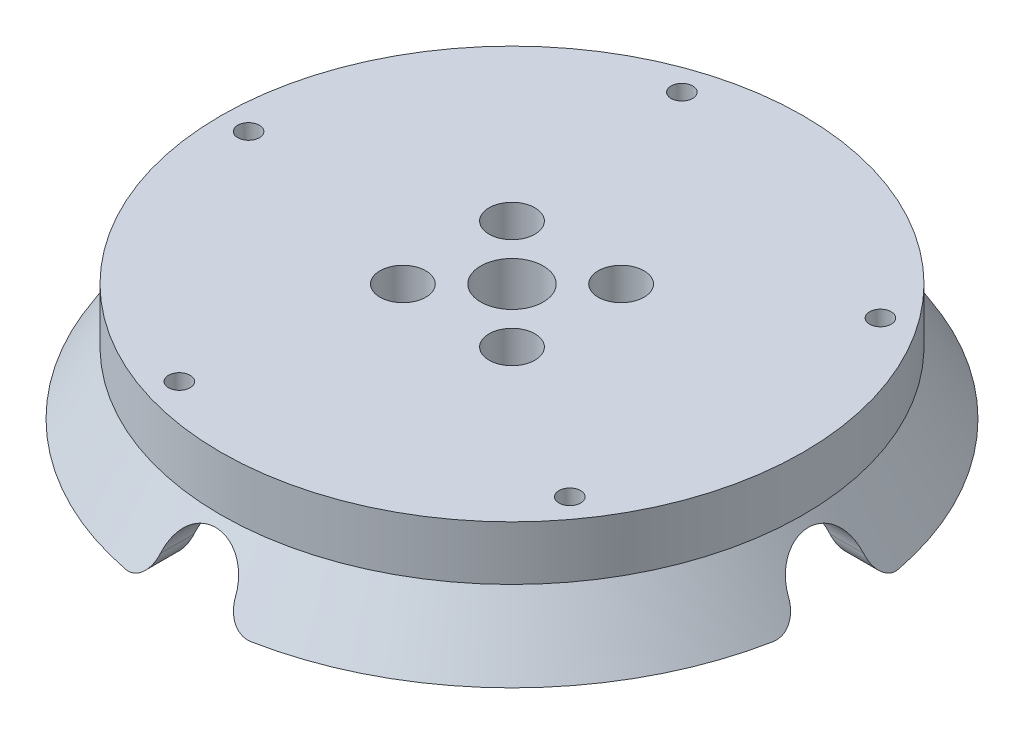
SolidWorks part; units mm, degrees
ref_plane "Front Plane" through (0, 0, 0) normal (0, 0, 1) x (1, 0, 0)
ref_plane "Top Plane" through (0, 0, 0) normal (0, 1, 0) x (1, 0, 0)
ref_plane "Right Plane" through (0, 0, 0) normal (1, 0, 0) x (0, 0, -1)
sketch "Sketch1" plane through (0, 0, 0) normal (0, 0, 1) x (1, 0, 0)
  line L0 (-79, -28) -> (-69.85, -13)
  line L1 (-79, -28) -> (-93.0535, -28) construction
  line L2 (-69.85, -13) -> (-69.85, 0)
  line L3 (-69.85, 0) -> (-7.5, 0)
  line L4 (-7.5, 0) -> (-7.5, -12)
  line L5 (-7.5, -12) -> (-26.5, -12)
  line L6 (0, 0) -> (0, -46.697) construction
  line L7 (-41.3597, -4) -> (-28.5, -13.0045)
  line L8 (-28.5, -13.0045) -> (-26.5, -13.0045)
  line L9 (-26.5, -13.0045) -> (-26.5, -12)
  line L10 (-41.3597, -4) -> (-56.36, -4)
  line L11 (-79, -28) -> (-71, -28)
  line L12 (-71, -28) -> (-56.36, -4)
  point P3 (-71.1944, -28)
  point P9 (-41.0578, -4)
  dimension "D2" = 15
  dimension "D3" = 139.7
  dimension "D4" = 13
  dimension "D6" = 15
  dimension "D8" = 2
  dimension "D9" = 53
  dimension "D5" = 12
  dimension "D7" = 8
  dimension "D10" = 4
  dimension "D11" = 1.0045
  dimension "D12" = 158
  dimension "D13" = 35
revolve "Revolve1" add sketch "Sketch1" angle 360 about L6
sketch "Sketch2" plane through (0, 0, 0) normal (0, 1, 0) x (1, 0, 0)
  circle A0 centre (-63.2499, 0.0912) radius 2.5975
  circle A1 centre (-19.4585, 60.1825) radius 2.5975
  circle A2 centre (51.2239, 37.1036) radius 2.5975
  circle A3 centre (51.1166, -37.2512) radius 2.5975
  circle A4 centre (-19.6321, -60.1261) radius 2.5975
  point P3 (0, 0)
  dimension "D1" = 5
extrude "Cut-Extrude1" cut sketch "Sketch2" against normal through all
sketch "Sketch3" plane through (0, -4, 0) normal (0, -1, 0) x (1, 0, 0)
  circle A0 centre (-63.2499, -0.0912) radius 4
  circle A2 centre (-19.6321, 60.1261) radius 4
  circle A3 centre (51.1166, 37.2512) radius 4
  circle A4 centre (51.2239, -37.1036) radius 4
  circle A5 centre (-19.4585, -60.1825) radius 4
  circle A18 centre (-63.2499, -0.0912) radius 2.5975 construction
  point P2 (-20.5632, 62.9779)
  point P5 (53.5411, 39.0181)
  point P6 (0, 0)
  point P15 (0, 0)
  point P17 (1.2868, -3.6499)
  point P19 (0, 0)
  point P20 (76.3609, 23.3459)
  point P21 (0, 0)
  point P22 (66.7979, 20.4222)
  point P23 (0, 0)
  point P24 (66.7979, 20.4222)
  point P25 (0, 0)
  point P26 (7.1723, 2.1928)
  point P27 (0, 0)
  point P28 (7.1723, 2.1928)
  point P29 (0, 0)
  point P30 (25.3421, 7.7479)
  point P31 (0, 0)
  point P32 (25.3421, 7.7479)
  point P33 (0, 0)
  point P34 (27.2547, 8.3326)
  point P35 (0, 0)
  point P36 (27.2547, 8.3326)
  point P37 (0, 0)
  point P38 (50.5407, 15.4518)
  point P39 (0, 0)
  point P40 (68.7105, 21.0069)
  dimension "D1" = 8
  dimension "D2" = 5
extrude "Cut-Extrude3" cut sketch "Sketch3" against normal offset from surface (30 mm away) 4 from offset 30 up to face at (-63.2499, 0, 2.5062)
sketch "Sketch8" plane through (0, 0, 0) normal (0, 0, 1) x (1, 0, 0)
  line L1 (-79, -28) -> (79, -28) construction
  line L2 (-15, -28) -> (15, -28)
  line L3 (69.85, -13) -> (-69.85, -13) construction
  arc A0 (9, -22.8) -> (-9, -22.8) centre (0, -24.0923) ccw
  arc A1 (9, -22.8) -> (15, -28) centre (15, -21.9385) ccw
  arc A2 (-15, -28) -> (-9, -22.8) centre (-15, -21.9385) ccw
  point P5 (0, 0)
  point P7 (0, -25.1589)
  point P12 (10, -18.8254)
  dimension "D1" = 18
  dimension "D2" = 30
  dimension "D3" = 2
extrude "Cut-Extrude6" cut sketch "Sketch8" against normal up to surface (32.7718 mm away) from offset 100 up to face at (-59.7995, -9.6898, 1.9323)
sketch "Sketch4" plane through (0, 0, 0) normal (0, 1, 0) x (1, 0, 0)
  circle A0 centre (13.0815, 13.0815) radius 2.55
  circle A2 centre (13.0815, -13.0815) radius 2.55
  circle A3 centre (-13.0815, -13.0815) radius 2.55
  circle A4 centre (-13.0815, 13.0815) radius 2.55
  circle A5 centre (-63.2499, 0.0912) radius 2.5975 construction
  point P2 (0, 0)
  point P11 (0, 0)
  point P16 (0, 0)
  point P17 (0, 0)
  point P18 (0, 0)
  dimension "D1" = 4
  dimension "D3" = 5.1
  dimension "D2" = 37
extrude "Cut-Extrude4" cut sketch "Sketch4" against normal through all
sketch "Sketch5" plane through (0, 0, 0) normal (0, 1, 0) x (1, 0, 0)
  circle A0 centre (13.0815, 13.0815) radius 5.5
  circle A1 centre (13.0815, -13.0815) radius 5.5
  circle A2 centre (-13.0815, -13.0815) radius 5.5
  circle A3 centre (-13.0815, 13.0815) radius 5.5
  circle A4 centre (13.0815, 13.0815) radius 2.55 construction
  circle A5 centre (13.0815, -13.0815) radius 2.55 construction
  circle A6 centre (-13.0815, -13.0815) radius 2.55 construction
  circle A7 centre (-13.0815, 13.0815) radius 2.55 construction
  point P14 (0, 0)
  dimension "D1" = 11
extrude "Cut-Extrude5" cut sketch "Sketch5" against normal offset from surface (8 mm away) 4 up to face at (-13.0815, -12, -15.6315)
pattern_circular "CirPattern1" count 4 over 360 about axis through (0, -12, 0) along (0, 1, 0) of "Cut-Extrude6"
equation "\"D4@Sketch1\"=12+1"
